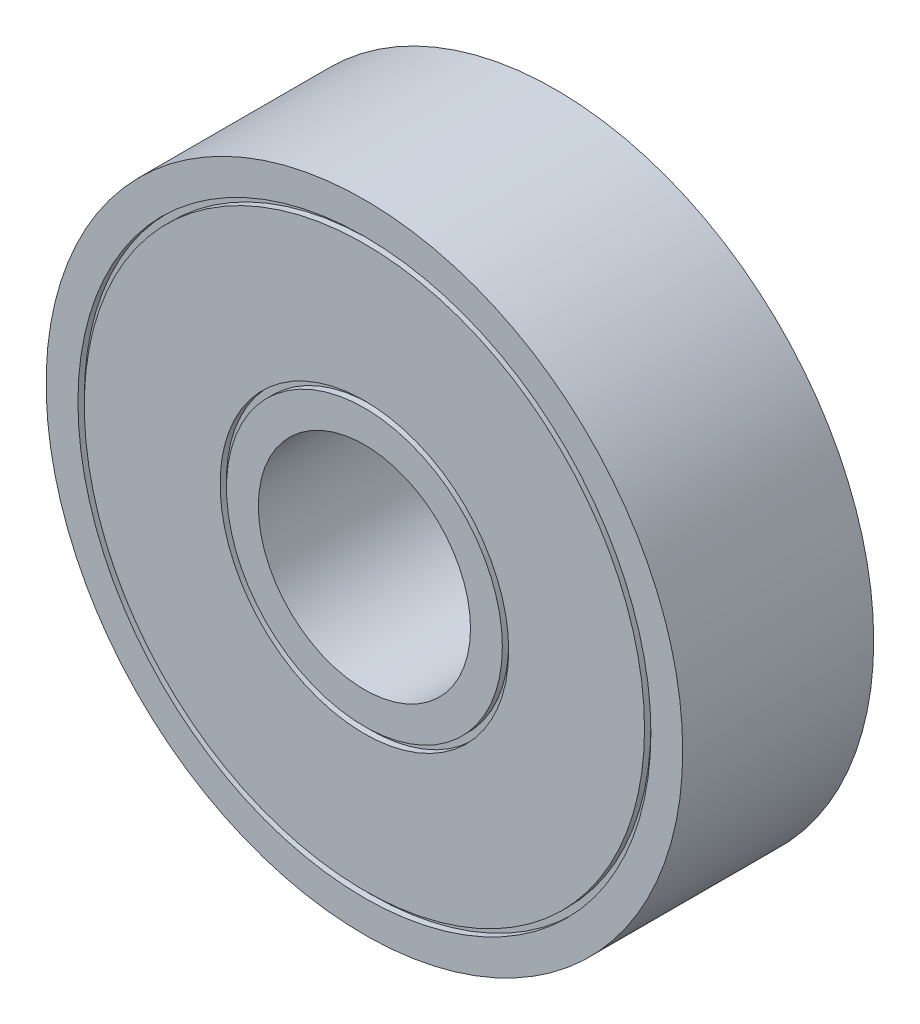
SolidWorks part; units mm, degrees
ref_plane "Alzado" through (0, 0, 0) normal (0, 0, 1) x (1, 0, 0)
ref_plane "Planta" through (0, 0, 0) normal (0, 1, 0) x (1, 0, 0)
ref_plane "Vista lateral" through (0, 0, 0) normal (1, 0, 0) x (0, 0, -1)
sketch "Croquis1" plane through (0, 0, 0) normal (0, 0, 1) x (1, 0, 0)
  circle A0 centre (0, 0) radius 15
  circle A1 centre (0, 0) radius 5
  dimension "D1" = 30
  dimension "D2" = 10
extrude "Saliente-Extruir1" add sketch "Croquis1" along normal blind 9
sketch "Croquis2" plane through (0, 0, 9) normal (0, 0, 1) x (1, 0, 0)
  circle A2 centre (0, 0) radius 13.5
  circle A3 centre (0, 0) radius 13.5
  circle A4 centre (0, 0) radius 13.2
  circle A5 centre (0, 0) radius 6.5
  circle A6 centre (0, 0) radius 6.5
  circle A7 centre (0, 0) radius 6.8
  dimension "D1" = 1.5
  dimension "D2" = 1.5
  dimension "D3" = 0.3
  dimension "D4" = 0.3
extrude "Cortar-Extruir1" cut sketch "Croquis2" against normal blind 0.3 contours A3 A4 | A7 A6 region at (-13.4618, 0, 9) region at (-6.6077, 0, 9)
ref_plane "Plano1" through (0, 0, 4.5) normal (0, 0, 1) x (1, 0, 0)
mirror "Simetría1" about plane through (0, 0, 4.5) normal (0, 0, 1) of "Cortar-Extruir1"
